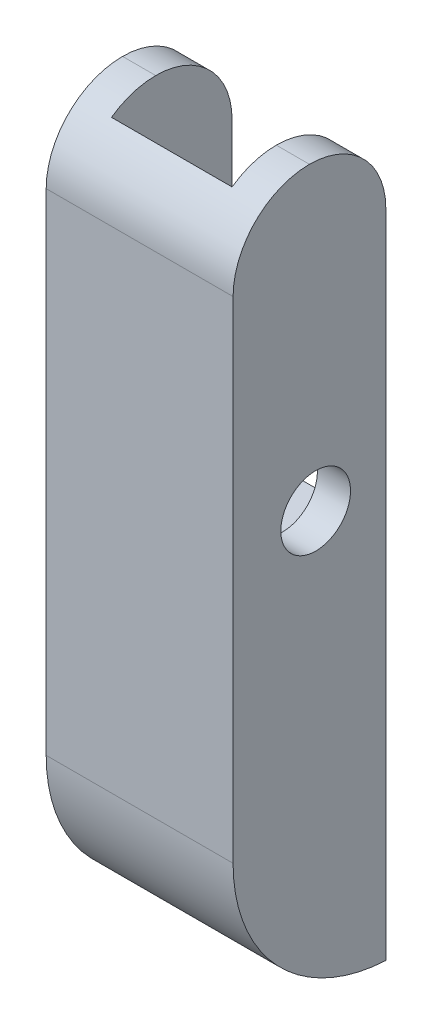
SolidWorks part; units mm, degrees
ref_plane "Front Plane" through (0, 0, 0) normal (0, 0, 1) x (1, 0, 0)
ref_plane "Top Plane" through (0, 0, 0) normal (0, 1, 0) x (1, 0, 0)
ref_plane "Right Plane" through (0, 0, 0) normal (1, 0, 0) x (0, 0, -1)
sketch "Sketch1" plane through (0, 0, 0) normal (0, 0, 1) x (1, 0, 0)
  line L1 (0, 0) -> (11.811, 0)
  line L2 (0, 0) -> (0, 45.9892)
  line L3 (0, 45.9892) -> (11.811, 45.9892)
  line L4 (11.811, 0) -> (11.811, 45.9892)
  dimension "D1" = 11.811
  dimension "D2" = 45.9892
extrude "Boss-Extrude1" add sketch "Sketch1" along normal blind 9.652 contours L2 L3 L4 L1
fillet "Fillet5" radius 4.826 1 edges at (5.9055, 45.9892, 0)
sketch "Sketch2" plane through (0, 0, 0) normal (0, 0, -1) x (-1, 0, 0)
  line L0 (0, 45.9892) -> (-11.811, 45.9892) construction
  line L1 (-9.7155, 45.9892) -> (-2.0955, 45.9892)
  line L2 (-9.7155, 45.9892) -> (-9.7155, 23.6372)
  line L3 (-9.7155, 23.6372) -> (-2.0955, 23.6372)
  line L4 (-2.0955, 45.9892) -> (-2.0955, 23.6372)
  line L5 (0, 0) -> (0, 41.1632) construction
  dimension "D1" = 22.352
  dimension "D2" = 7.62
  dimension "D3" = 2.0955
extrude "Cut-Extrude1" cut sketch "Sketch2" against normal blind 7.62
sketch "Sketch3" plane through (0, 0, 0) normal (-1, 0, 0) x (0, 0, 1)
  line L0 (7.62, 45.9892) -> (7.62, 23.6372) construction
  line L2 (7.62, 23.6372) -> (0, 23.6372) construction
  circle A0 centre (4.4323, 26.8249) radius 2.2035
  dimension "D1" = 3.1877
  dimension "D3" = 4.4069
  dimension "D2" = 3.1877
extrude "Cut-Extrude2" cut sketch "Sketch3" against normal through all and the other way through all
fillet "Fillet4" radius 4.826 1 edges at (5.9055, 45.9892, 9.652)
fillet "Fillet6" radius 10.16 1 edges at (5.9055, 0, 9.652)
